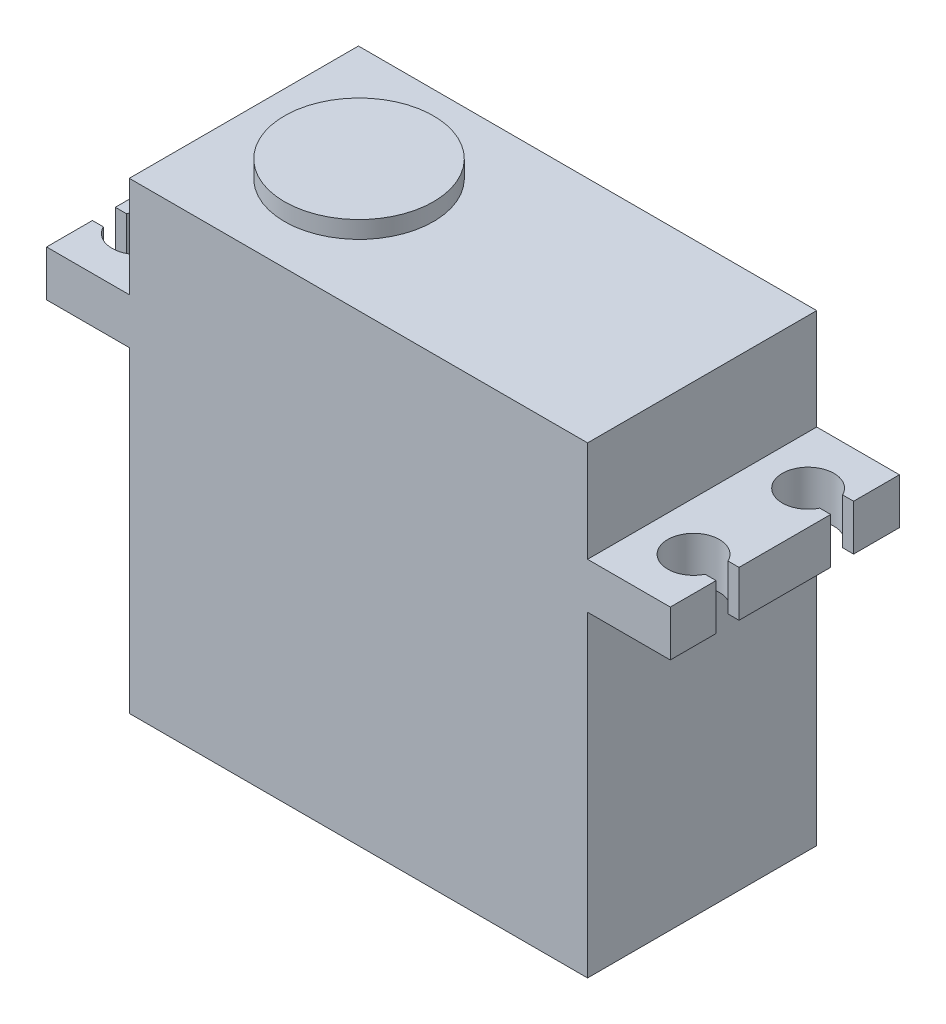
SolidWorks part; units mm, degrees
ref_plane "Front Plane" through (0, 0, 0) normal (0, 0, 1) x (1, 0, 0)
ref_plane "Top Plane" through (0, 0, 0) normal (0, 1, 0) x (1, 0, 0)
ref_plane "Right Plane" through (0, 0, 0) normal (1, 0, 0) x (0, 0, -1)
sketch "Sketch2" plane through (0, 0, 0) normal (0, 1, 0) x (1, 0, 0)
  line L1 (-20, -10) -> (20, -10)
  line L2 (-20, -10) -> (-20, 10)
  line L3 (-20, 10) -> (20, 10)
  line L4 (20, -10) -> (20, 10)
  line L5 (-20, -10) -> (20, 10) construction
  line L6 (-20, 10) -> (20, -10) construction
  point P0 (0, 0)
  dimension "D1" = 20
  dimension "D2" = 40
extrude "Boss-Extrude1" add sketch "Sketch2" along normal blind 27.65
sketch "Sketch3" plane through (-20, 0, 0) normal (-1, 0, 0) x (0, 0, 1)
  line L0 (0, 0) -> (0, 4) construction
  line L1 (-10, 0) -> (10, 0) construction
  line L3 (-3.5, 8) -> (3.5, 8)
  line L4 (-3.5, 8) -> (-3.5, 4)
  line L5 (-3.5, 4) -> (3.5, 4)
  line L6 (3.5, 8) -> (3.5, 4)
  line L7 (-3.5, 8) -> (3.5, 4) construction
  line L8 (-3.5, 4) -> (3.5, 8) construction
  point P4 (0, 6)
  dimension "D1" = 4
  dimension "D2" = 7
extrude "Boss-Extrude2" add sketch "Sketch3" along normal blind 5
sketch "Sketch5" plane through (0, 27.65, 0) normal (0, 1, 0) x (1, 0, 0)
  line L4 (20, -10) -> (20, 10)
  line L5 (20, 10) -> (-20, 10)
  line L6 (-20, 10) -> (-20, -10)
  line L7 (-20, -10) -> (20, -10)
  line L8 (20, -10) -> (20, 10)
  line L9 (20, 10) -> (-20, 10)
  line L10 (-20, 10) -> (-20, -10)
  line L11 (-20, -10) -> (20, -10)
  dimension "D1" = 0
extrude "Boss-Extrude5" add sketch "Sketch5" along normal blind 12.8
sketch "Sketch7" plane through (-20, 0, 0) normal (-1, 0, 0) x (0, 0, 1)
  line L0 (-10, 27.65) -> (10, 27.65)
  line L1 (10, 27.65) -> (10, 31.65)
  line L2 (10, 40.45) -> (10, 0) construction
  line L3 (-10, 31.65) -> (-10, 27.65)
  line L4 (-10, 40.45) -> (-10, 0) construction
  line L5 (10, 31.65) -> (-10, 31.65)
  dimension "D1" = 4
extrude "Boss-Extrude6" add sketch "Sketch7" along normal blind 7.22
sketch "Sketch8" plane through (0, 31.65, 0) normal (0, 1, 0) x (1, 0, 0)
  line L0 (-20, 10) -> (-20, 0) construction
  line L1 (-20, 0) -> (-27.22, 0) construction
  line L2 (-27.22, -10) -> (-27.22, 10) construction
  line L3 (-20, 5) -> (-27.22, 5) construction
  line L4 (-26.2656, 6) -> (-27.22, 6)
  line L8 (-27.22, 6) -> (-27.22, 4)
  line L9 (-27.22, 4) -> (-26.2656, 4)
  arc A1 (-26.2656, 4) -> (-26.2656, 6) centre (-24.25, 5) ccw
  dimension "D1" = 4.25
  dimension "D3" = 4.5
  dimension "D2" = 1
extrude "Cut-Extrude3" cut sketch "Sketch8" against normal blind 4
mirror "Mirror10" about plane through (0, 0, 0) normal (0, 0, 1) of "Cut-Extrude3"
mirror "Mirror11" about plane through (0, 0, 0) normal (1, 0, 0) of "Mirror10", "Cut-Extrude3", "Boss-Extrude6"
sketch "Sketch9" plane through (0, 40.45, 0) normal (0, 1, 0) x (1, 0, 0)
  line L0 (20, 0) -> (-20, 0) construction
  line L1 (20, -10) -> (20, 10) construction
  line L2 (-20, 10) -> (-20, -10) construction
  line L5 (-9.95, 0) -> (-9.95, 8.0914) construction
  circle A1 centre (-9.95, 0) radius 6.5
  circle A2 centre (-9.95, 0) radius 3
  dimension "D1" = 13
  dimension "D3" = 6
  dimension "D2" = 29.95
extrude "Boss-Extrude8" add sketch "Sketch9" along normal blind 1.5 contours A1 A2 | A2 region at (-16.2662, 40.45, 0)
